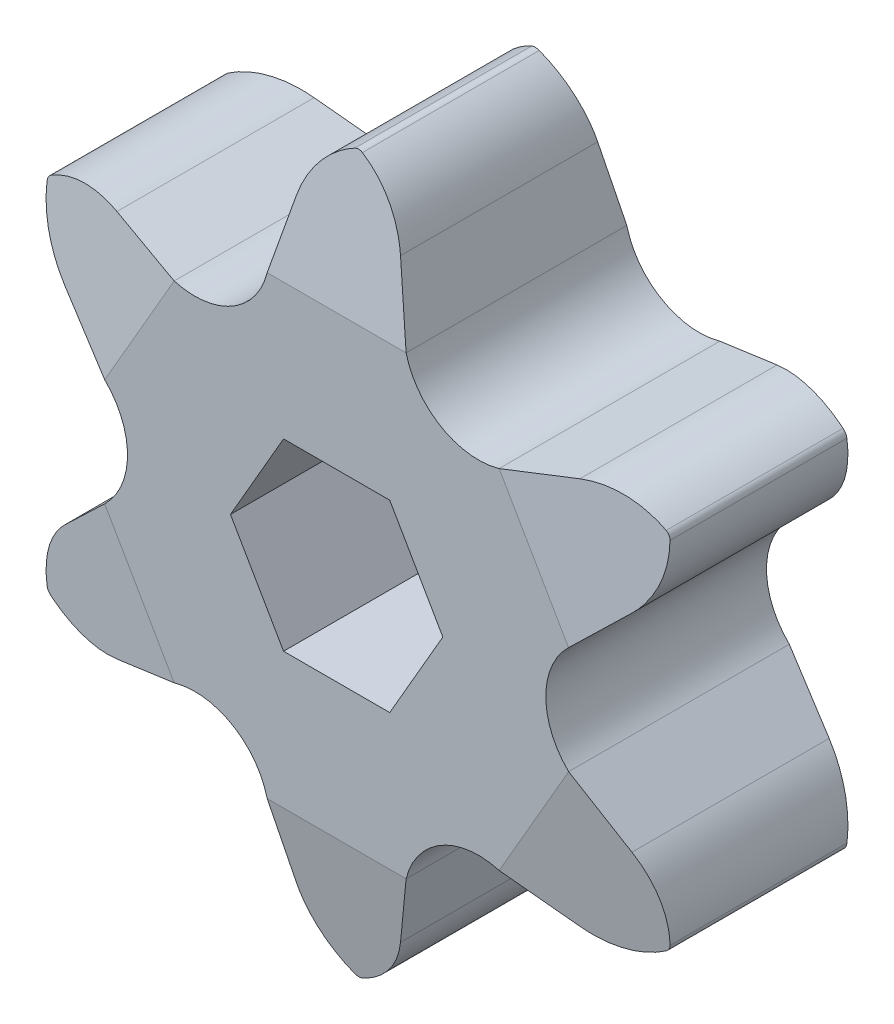
SolidWorks part; units mm, degrees
ref_plane "Front Plane" through (0, 0, 0) normal (0, 0, 1) x (1, 0, 0)
ref_plane "Top Plane" through (0, 0, 0) normal (0, 1, 0) x (1, 0, 0)
ref_plane "Right Plane" through (0, 0, 0) normal (1, 0, 0) x (0, 0, -1)
sketch "Sketch1" plane through (0, 0, 0) normal (0, 0, 1) x (1, 0, 0)
  line L0 (-5.0267, 5.911) -> (-7.4077, 6.5937)
  line L1 (-9.2066, 3.4779) -> (-7.4249, 1.7573)
  line L2 (2.9817, 7.7655) -> (2.3825, 10.1689)
  line L3 (-1.2153, 10.1689) -> (-1.8146, 7.7655)
  line L4 (8.592, 1.7573) -> (10.3738, 3.4779)
  line L5 (8.5749, 6.5937) -> (6.1938, 5.911)
  line L6 (6.1938, -6.1055) -> (8.5749, -6.7882)
  line L7 (10.3738, -3.6724) -> (8.592, -1.9518)
  line L8 (-1.8146, -7.96) -> (-1.2153, -10.3634)
  line L9 (2.3825, -10.3634) -> (2.9817, -7.96)
  line L10 (-7.4249, -1.9518) -> (-9.2066, -3.6724)
  line L11 (-7.4077, -6.7882) -> (-5.0267, -6.1055)
  arc A0 (-7.1314, 1.42) -> (-7.4249, 1.7573) centre (-9.2158, -0.0973) ccw
  arc A1 (-10.0364, 6.1886) -> (-10.1701, 5.9569) centre (-9.8707, 5.9385) ccw
  arc A2 (-4.5879, 5.8255) -> (-1.9599, 7.3427) centre (-4.3161, 8.3892) ccw
  arc A3 (-5.0267, 5.911) -> (-4.5879, 5.8255) centre (-4.3161, 8.3892) ccw
  arc A4 (-7.4077, 6.5937) -> (-10.0364, 6.1886) centre (-8.2829, 3.5417) ccw
  arc A5 (-10.1701, 5.9569) -> (-9.2066, 3.4779) centre (-7.0011, 5.7618) ccw
  arc A6 (-1.9599, 7.3427) -> (-1.8146, 7.7655) centre (-4.3161, 8.3892) ccw
  arc A7 (0.7173, 12.2428) -> (0.4498, 12.2428) centre (0.5836, 11.9742) ccw
  arc A8 (3.127, 7.3427) -> (5.755, 5.8255) centre (5.4832, 8.3892) ccw
  arc A9 (2.9817, 7.7655) -> (3.127, 7.3427) centre (5.4832, 8.3892) ccw
  arc A10 (2.3825, 10.1689) -> (0.7173, 12.2428) centre (-0.6982, 9.4008) ccw
  arc A11 (0.4498, 12.2428) -> (-1.2153, 10.1689) centre (1.8653, 9.4008) ccw
  arc A12 (5.755, 5.8255) -> (6.1938, 5.911) centre (5.4832, 8.3892) ccw
  arc A13 (11.3372, 5.9569) -> (11.2035, 6.1886) centre (11.0378, 5.9385) ccw
  arc A14 (8.2985, 1.42) -> (8.2985, -1.6145) centre (10.3829, -0.0973) ccw
  arc A15 (8.592, 1.7573) -> (8.2985, 1.42) centre (10.3829, -0.0973) ccw
  arc A16 (10.3738, 3.4779) -> (11.3372, 5.9569) centre (8.1682, 5.7618) ccw
  arc A17 (11.2035, 6.1886) -> (8.5749, 6.5937) centre (9.45, 3.5417) ccw
  arc A18 (8.2985, -1.6145) -> (8.592, -1.9518) centre (10.3829, -0.0973) ccw
  arc A19 (11.2035, -6.3831) -> (11.3372, -6.1514) centre (11.0378, -6.133) ccw
  arc A20 (5.755, -6.02) -> (3.127, -7.5373) centre (5.4832, -8.5837) ccw
  arc A21 (6.1938, -6.1055) -> (5.755, -6.02) centre (5.4832, -8.5837) ccw
  arc A22 (8.5749, -6.7882) -> (11.2035, -6.3831) centre (9.45, -3.7362) ccw
  arc A23 (11.3372, -6.1514) -> (10.3738, -3.6724) centre (8.1682, -5.9563) ccw
  arc A24 (3.127, -7.5373) -> (2.9817, -7.96) centre (5.4832, -8.5837) ccw
  arc A25 (0.4498, -12.4373) -> (0.7173, -12.4373) centre (0.5836, -12.1688) ccw
  arc A26 (-1.9599, -7.5373) -> (-4.5879, -6.02) centre (-4.3161, -8.5837) ccw
  arc A27 (-1.8146, -7.96) -> (-1.9599, -7.5373) centre (-4.3161, -8.5837) ccw
  arc A28 (-1.2153, -10.3634) -> (0.4498, -12.4373) centre (1.8653, -9.5953) ccw
  arc A29 (0.7173, -12.4373) -> (2.3825, -10.3634) centre (-0.6982, -9.5953) ccw
  arc A30 (-4.5879, -6.02) -> (-5.0267, -6.1055) centre (-4.3161, -8.5837) ccw
  arc A31 (-10.1701, -6.1514) -> (-10.0364, -6.3831) centre (-9.8707, -6.133) ccw
  arc A32 (-7.1314, -1.6145) -> (-7.1314, 1.42) centre (-9.2158, -0.0973) ccw
  arc A33 (-7.4249, -1.9518) -> (-7.1314, -1.6145) centre (-9.2158, -0.0973) ccw
  arc A34 (-9.2066, -3.6724) -> (-10.1701, -6.1514) centre (-7.0011, -5.9563) ccw
  arc A35 (-10.0364, -6.3831) -> (-7.4077, -6.7882) centre (-8.2829, -3.7362) ccw
  dimension "D1" = 2.5781
  dimension "D2" = 0.3
  dimension "D3" = 3.175
  dimension "D4" = 0.4498
  dimension "D5" = 0.5836
  dimension "D6" = 8.5749
  dimension "D7" = 8.592
  dimension "D8" = 11.0378
  dimension "D9" = 11.2035
  dimension "D10" = 1.9599
  dimension "D11" = 4.3161
  dimension "D12" = 7.0011
  dimension "D13" = 7.1314
  dimension "D14" = 3.4779
  dimension "D15" = 5.8255
extrude "Boss-Extrude1" add sketch "Sketch1" along normal mid plane 7.62
ref_plane "Plane1" through (0.5845, -0.0063, 0) normal (0.9999, -0.0108, 0) x (0, 0, -1)
ref_plane "Plane2" through (0.194, -0.3278, 0) normal (-0.5094, 0.8606, 0) x (0.8606, 0.5094, 0)
ref_axis "Axis1" through (0.5836, -0.0973, -4.191) along (0, 0, 1)
sketch "Sketch2" plane through (0, 0, 0) normal (1, 0, 0) x (0, 0, -1)
  line L0 (-3.048, 12.2742) -> (-3.81, 7.7655)
  line L1 (3.81, 12.2742) -> (-3.81, 12.2742) construction
  line L2 (-3.81, 7.7655) -> (-3.81, 12.2742)
  line L3 (-3.81, 12.2742) -> (-3.048, 12.2742)
  dimension "D1" = 0.762
extrude "Cut-Extrude1" cut sketch "Sketch2" against normal through all both and the other way through all
pattern_circular "CirPattern1" count 6 over 360 about axis through (0.5836, -0.0973, -4.191) along (0, 0, 1) of "Cut-Extrude1"
mirror "Mirror1" about plane through (0, 0, 0) normal (0, 0, 1) of "Cut-Extrude1", "CirPattern1"
sketch "Sketch4" plane through (0, 0, 3.81) normal (0, 0, 1) x (1, 0, 0)
  circle A0 centre (0.5836, -0.0973) radius 4.7625
  dimension "D1" = 9.525
extrude "Boss-Extrude2" [suppressed] add sketch "Sketch4" along normal mid plane 6.35
chamfer "Chamfer1" [suppressed] distance 3.175 distance2 1.27
sketch "Sketch3" plane through (0, 0, -3.81) normal (0, 0, -1) x (-1, 0, 0)
  line L1 (1.2495, -3.2723) -> (3.0826, -0.0973)
  line L2 (3.0826, -0.0973) -> (1.2495, 3.0777)
  line L3 (1.2495, 3.0777) -> (-2.4166, 3.0777)
  line L4 (-2.4166, 3.0777) -> (-4.2497, -0.0973)
  line L5 (-4.2497, -0.0973) -> (-2.4166, -3.2723)
  line L6 (-2.4166, -3.2723) -> (1.2495, -3.2723)
  circle A0 centre (-0.5836, -0.0973) radius 3.175 construction
  dimension "D1" = 6.35
extrude "Cut-Extrude2" cut sketch "Sketch3" against normal through all both and the other way through all
